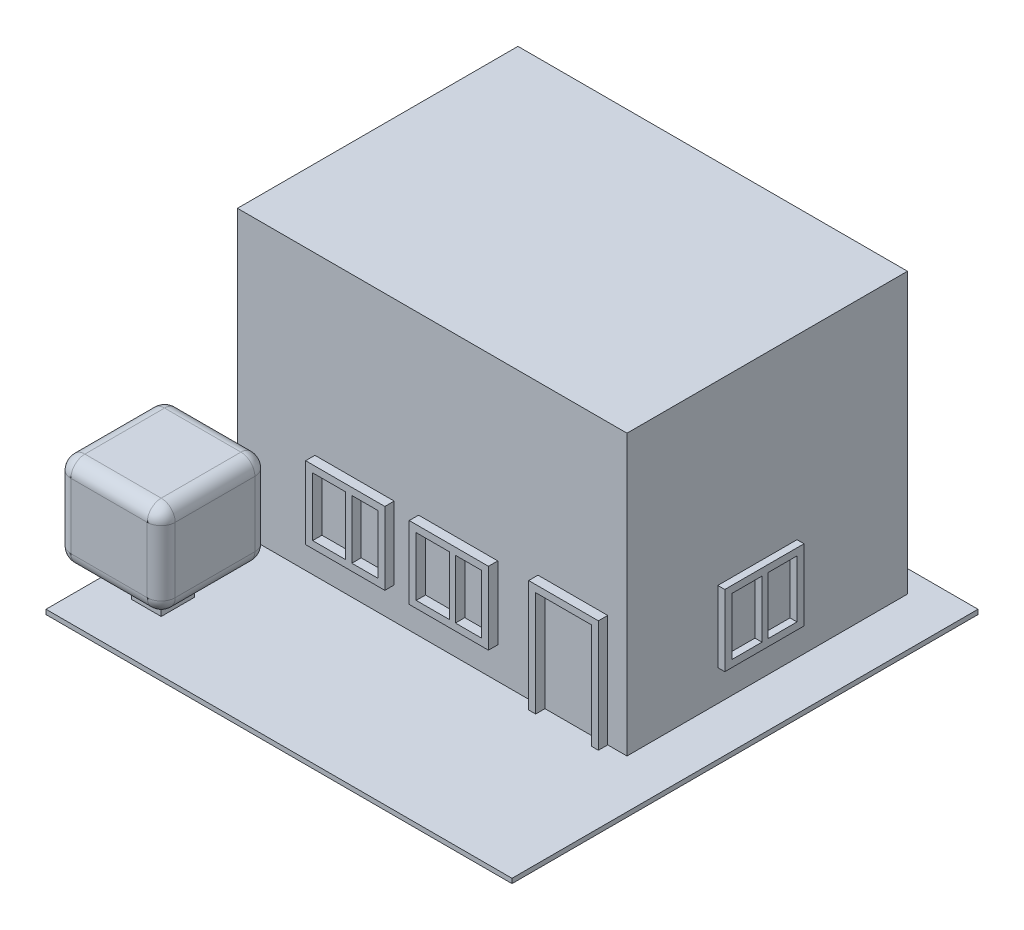
SolidWorks part; units mm, degrees
ref_plane "Plano frontal" through (0, 0, 0) normal (0, 0, 1) x (1, 0, 0)
ref_plane "Plano superior" through (0, 0, 0) normal (0, 1, 0) x (1, 0, 0)
ref_plane "Plano direito" through (0, 0, 0) normal (1, 0, 0) x (0, 0, -1)
sketch "Esboço1" plane through (0, 0, 0) normal (0, 1, 0) x (1, 0, 0)
  line L1 (-0.5, -0.5) -> (0.5, -0.5)
  line L2 (-0.5, -0.5) -> (-0.5, 0.5)
  line L3 (-0.5, 0.5) -> (0.5, 0.5)
  line L4 (0.5, -0.5) -> (0.5, 0.5)
  line L5 (-0.5, -0.5) -> (0.5, 0.5) construction
  line L6 (-0.5, 0.5) -> (0.5, -0.5) construction
  point P0 (0, 0)
  dimension "D1" = 1
  dimension "D2" = 1
extrude "Ressalto-extrusão1" add sketch "Esboço1" along normal blind 0.01
sketch "Esboço2" plane through (0, 0.01, 0) normal (0, 1, 0) x (1, 0, 0)
  line L1 (0.3962, 0.4525) -> (-0.4397, 0.4525)
  line L2 (0.3962, 0.4525) -> (0.3962, -0.1494)
  line L3 (0.3962, -0.1494) -> (-0.4397, -0.1494)
  line L4 (-0.4397, 0.4525) -> (-0.4397, -0.1494)
  line L5 (0.3962, 0.4525) -> (-0.4397, -0.1494) construction
  line L6 (0.3962, -0.1494) -> (-0.4397, 0.4525) construction
  point P0 (-0.0218, 0.1515)
extrude "Ressalto-extrusão3" add sketch "Esboço2" along normal blind 0.3
sketch "Esboço6" plane through (0, 0, 0.1494) normal (0, 0, 1) x (1, 0, 0)
  line L1 (0.2202, 0.01) -> (0.3398, 0.01)
  line L2 (0.2202, 0.01) -> (0.2202, 0.2356)
  line L3 (0.2202, 0.2356) -> (0.3398, 0.2356)
  line L4 (0.3398, 0.01) -> (0.3398, 0.2356)
  line L7 (-0.4397, 0.01) -> (0.3962, 0.01) construction
  line L8 (0.2052, 0.01) -> (0.2052, 0.2506)
  line L9 (0.2052, 0.2506) -> (0.3548, 0.2506)
  line L10 (0.3548, 0.01) -> (0.3548, 0.2506)
  line L11 (-0.2734, 0.234) -> (-0.1034, 0.234)
  line L12 (-0.2584, 0.219) -> (-0.1874, 0.219)
  line L13 (-0.2584, 0.219) -> (-0.2584, 0.0931)
  line L14 (-0.2584, 0.0931) -> (-0.1874, 0.0931)
  line L15 (-0.1184, 0.219) -> (-0.1184, 0.0931)
  line L20 (-0.1034, 0.234) -> (-0.1034, 0.0781)
  line L21 (-0.2734, 0.0781) -> (-0.1034, 0.0781)
  line L22 (-0.2734, 0.234) -> (-0.2734, 0.0781)
  line L27 (-0.1874, 0.219) -> (-0.1874, 0.0931)
  line L28 (-0.1743, 0.219) -> (-0.1743, 0.0931)
  line L29 (-0.1743, 0.219) -> (-0.1184, 0.219)
  line L30 (-0.2584, 0.219) -> (-0.1184, 0.219) construction
  line L31 (-0.1743, 0.0931) -> (-0.1184, 0.0931)
  line L32 (-0.2584, 0.0931) -> (-0.1184, 0.0931) construction
  line L33 (-0.0511, 0.234) -> (0.1189, 0.234)
  line L34 (-0.0361, 0.219) -> (0.0349, 0.219)
  line L35 (-0.0361, 0.219) -> (-0.0361, 0.0931)
  line L36 (-0.0361, 0.0931) -> (0.0349, 0.0931)
  line L37 (0.1039, 0.219) -> (0.1039, 0.0931)
  line L38 (0.1189, 0.234) -> (0.1189, 0.0781)
  line L39 (-0.0511, 0.0781) -> (0.1189, 0.0781)
  line L40 (-0.0511, 0.234) -> (-0.0511, 0.0781)
  line L41 (0.0349, 0.219) -> (0.0349, 0.0931)
  line L42 (0.048, 0.219) -> (0.048, 0.0931)
  line L43 (0.048, 0.219) -> (0.1039, 0.219)
  line L44 (0.048, 0.0931) -> (0.1039, 0.0931)
  line M42 (-0.4397, 0.01) -> (0.3962, 0.01)
  dimension "D2" = 0.14
  dimension "D3" = 2
  dimension "D1" = 0.015
  dimension "D4" = 0.015
sketch "Esboço7" plane through (-0.4397, 0, 0) normal (-1, 0, 0) x (0, 0, 1)
  line L0 (-0.2432, 0.2339) -> (-0.0732, 0.2339)
  line L1 (-0.2282, 0.2189) -> (-0.1634, 0.2189)
  line L2 (-0.2282, 0.2189) -> (-0.2282, 0.0961)
  line L3 (-0.2282, 0.0961) -> (-0.1634, 0.0961)
  line L4 (-0.0882, 0.2189) -> (-0.0882, 0.0961)
  line L5 (-0.0732, 0.2339) -> (-0.0732, 0.0811)
  line L6 (-0.2432, 0.0811) -> (-0.0732, 0.0811)
  line L7 (-0.2432, 0.2339) -> (-0.2432, 0.0811)
  line L8 (-0.1634, 0.2189) -> (-0.1634, 0.0961)
  line L9 (-0.1502, 0.2189) -> (-0.1502, 0.0961)
  line L10 (-0.1502, 0.2189) -> (-0.0882, 0.2189)
  line L11 (-0.1502, 0.0961) -> (-0.0882, 0.0961)
  dimension "D1" = 0.14
sketch "Esboço8" plane through (0.3962, 0, 0) normal (1, 0, 0) x (0, 0, -1)
  line L0 (0.0455, 0.2296) -> (0.2155, 0.2296)
  line L1 (0.0605, 0.2146) -> (0.1252, 0.2146)
  line L2 (0.0605, 0.2146) -> (0.0605, 0.0918)
  line L3 (0.0605, 0.0918) -> (0.1252, 0.0918)
  line L4 (0.2005, 0.2146) -> (0.2005, 0.0918)
  line L5 (0.2155, 0.2296) -> (0.2155, 0.0768)
  line L6 (0.0455, 0.0768) -> (0.2155, 0.0768)
  line L7 (0.0455, 0.2296) -> (0.0455, 0.0768)
  line L8 (0.1252, 0.2146) -> (0.1252, 0.0918)
  line L9 (0.1384, 0.2146) -> (0.1384, 0.0918)
  line L10 (0.1384, 0.2146) -> (0.2005, 0.2146)
  line L11 (0.1384, 0.0918) -> (0.2005, 0.0918)
  dimension "D1" = 0.14
extrude "Ressalto-extrusão7" add sketch "Esboço8" along normal blind 0.015
extrude "Ressalto-extrusão8" add sketch "Esboço7" along normal blind 0.015
sketch "Esboço9" plane through (0, 0.01, 0) normal (0, 1, 0) x (1, 0, 0)
  line L1 (-0.4267, -0.3189) -> (-0.3629, -0.3189)
  line L2 (-0.4267, -0.3189) -> (-0.4267, -0.3899)
  line L3 (-0.4267, -0.3899) -> (-0.3629, -0.3899)
  line L4 (-0.3629, -0.3189) -> (-0.3629, -0.3899)
extrude "Ressalto-extrusão10" add sketch "Esboço9" along normal blind 0.07
sketch "Esboço11" plane through (0, 0.08, 0) normal (0, 1, 0) x (1, 0, 0)
  line L18 (-0.5067, -0.2389) -> (-0.5067, -0.4699)
  line L19 (-0.5067, -0.4699) -> (-0.2829, -0.4699)
  line L20 (-0.2829, -0.4699) -> (-0.2829, -0.2389)
  line L21 (-0.2829, -0.2389) -> (-0.5067, -0.2389)
  line L22 (-0.5067, -0.2389) -> (-0.5067, -0.4699)
  line L23 (-0.5067, -0.4699) -> (-0.2829, -0.4699)
  line L24 (-0.2829, -0.4699) -> (-0.2829, -0.2389)
  line L25 (-0.2829, -0.2389) -> (-0.5067, -0.2389)
  dimension "D1" = 0.08
extrude "Ressalto-extrusão11" add sketch "Esboço11" along normal blind 0.2
fillet "Filete2" radius 0.03 9 edges at (-0.2829, 0.18, 0.4699) (-0.3948, 0.08, 0.4699) (-0.2829, 0.28, 0.3544) (-0.3948, 0.28, 0.4699) (-0.3948, 0.28, 0.2389) (-0.5067, 0.18, 0.2389) (-0.5067, 0.28, 0.3544) (-0.5067, 0.18, 0.4699) (-0.5067, 0.08, 0.3544)
fillet "Filete3" radius 0.03 6 edges at (-0.4979, 0.0888, 0.2477) (-0.2916, 0.2712, 0.2477) (-0.2916, 0.0888, 0.4611) (-0.3798, 0.08, 0.2389) (-0.2829, 0.165, 0.2389) (-0.2829, 0.08, 0.3394)
extrude "Ressalto-extrusão12" add sketch "Esboço6" along normal blind 0.02 contours L33 L40 L39 L38 L44 L42 L43 L37 L34 L41 L36 L35 | L10 L9 L8 L2 L3 L4 M42 | L11 L22 L21 L20 L31 L28 L29 L15 L12 L27 L14 L13 region at (0.2127, 0.0128, 0.1494) region at (-0.1873, 0.156, 0.1494) region at (0.0351, 0.156, 0.1494)
sketch "Esboço12" plane through (0, 0.31, 0) normal (0, 1, 0) x (1, 0, 0)
  line L0 (-0.4397, 0.4525) -> (-0.4397, -0.1494) construction
  line L1 (0.3962, 0.4525) -> (-0.4397, 0.4525) construction
  line L2 (-0.4397, -0.1494) -> (0.3962, -0.1494) construction
  line L3 (0.3962, -0.1494) -> (0.3962, 0.4525) construction
  line L4 (-0.4397, 0.4525) -> (-0.4397, -0.1494)
  line L5 (0.3962, 0.4525) -> (-0.4397, 0.4525)
  line L6 (-0.4397, -0.1494) -> (0.3962, -0.1494)
  line L7 (0.3962, -0.1494) -> (0.3962, 0.4525)
extrude "Ressalto-extrusão13" add sketch "Esboço12" along normal blind 0.3
